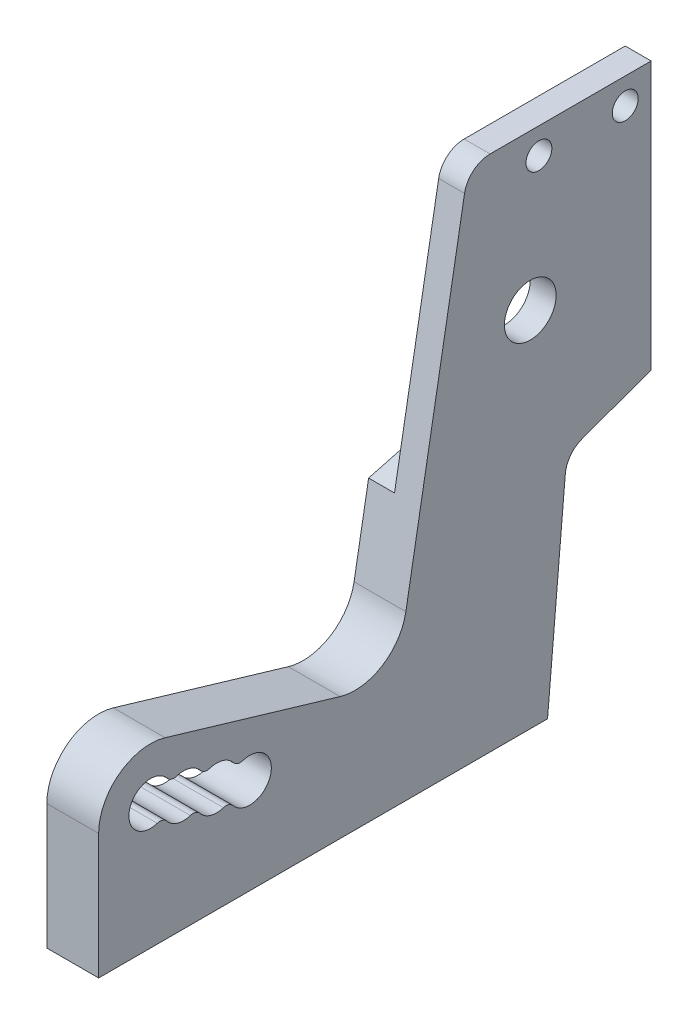
SolidWorks part; units mm, degrees
material "1060 Alloy"
ref_plane "Front Plane" through (0, 0, 0) normal (0, 0, 1) x (1, 0, 0)
ref_plane "Top Plane" through (0, 0, 0) normal (0, 1, 0) x (1, 0, 0)
ref_plane "Right Plane" through (0, 0, 0) normal (1, 0, 0) x (0, 0, -1)
sketch "Sketch1" plane through (0, 0, 0) normal (1, 0, 0) x (0, 0, -1)
  line L1 (0, 0) -> (64, 0)
  line L2 (0, 0) -> (0, 60)
  line L3 (0, 60) -> (64, 60)
  line L4 (64, 0) -> (64, 60)
  circle A0 centre (6, 14.5) radius 2.5
  circle A1 centre (50, 42) radius 3
  dimension "D1" = 6
  dimension "D2" = 5
  dimension "D3" = 14.5
  dimension "D4" = 6
  dimension "D5" = 42
  dimension "D6" = 50
  dimension "D7" = 64
  dimension "D8" = 60
extrude "Boss-Extrude1" add sketch "Sketch1" along normal blind 6
sketch "Sketch2" plane through (6, 0, 0) normal (1, 0, 0) x (0, 0, -1)
  line L0 (0, 60) -> (0, 0) construction
  line L1 (0, 0) -> (64, 0) construction
  line L2 (7.7045, 20.2528) -> (27.9735, 14.2472)
  line L4 (0, 14.5) -> (0, 61)
  line L5 (0, 61) -> (43, 61)
  line L6 (43, 61) -> (35.5869, 18.9581)
  line L7 (64, 60) -> (0, 60) construction
  arc A0 (0, 14.5) -> (7.7045, 20.2528) centre (6, 14.5) cw
  circle A1 centre (50, 42) radius 5 construction
  circle A2 centre (6, 14.5) radius 2.5 construction
  arc A4 (27.9735, 14.2472) -> (35.5869, 18.9581) centre (29.678, 20) ccw
  dimension "D2" = 10
  dimension "D4" = 80
  dimension "D1" = 1
  dimension "D3" = 43
  dimension "D5" = 20
extrude "Cut-Extrude1" cut sketch "Sketch2" against normal up to next
sketch "Sketch3" plane through (6, 0, 0) normal (1, 0, 0) x (0, 0, -1)
  line L2 (0, 0) -> (64, 0) construction
  line L57 (64, 0) -> (52, 0)
  line L58 (64, 0) -> (64, 29)
  line L59 (64, 29) -> (54.2259, 25.4425)
  line L60 (52, 0) -> (54.2259, 25.4425)
  dimension "D1" = 52
  dimension "D2" = 29
  dimension "D3" = 70
  dimension "D4" = 85
extrude "Cut-Extrude2" cut sketch "Sketch3" against normal up to next
fillet "Fillet1" radius 3 1 edges at (3, 60, -42.8237)
fillet "Fillet2" radius 3 1 edges at (3, 25.4425, -54.2259)
hole_wizard "Tap Drill for M3 Tap1" positions "Sketch5" profile "Sketch4" hole size "M3" standard "ISO"
sketch "Sketch5" plane through (0, 0, 0) normal (0, -1, 0) x (-1, 0, 0)
  line L1 (-6, 0) -> (0, 0) construction
  line L2 (-6, 0) -> (-6, 52) construction
  point P0 (-3, 46)
  point P2 (-3, 10)
  dimension "D1" = 3
  dimension "D2" = 10
  dimension "D3" = 36
sketch "Sketch4" plane through (3, 0, -46) normal (1, 0, 0) x (0, 0, -1)
  line L0 (0, 0) -> (0, 9.7511)
  line L1 (0, 9.7511) -> (1.25, 9)
  line L2 (1.25, 9) -> (1.25, 0)
  line L5 (1.25, 0) -> (0, 0)
  line L10 (0, 9.7511) -> (-1.25, 9) construction
  line L11 (0, -6.35) -> (0, 107.95) construction
  dimension "Hole Dia." = 2.5
  dimension "Hole Depth" = 9
  dimension "Drill Angle" = 118
sketch "Sketch9" plane through (0, 0, 0) normal (-1, 0, 0) x (0, 0, 1)
  line L0 (-64, 60) -> (-64, 33)
  line L1 (-64, 60) -> (-45.341, 60) construction
  line L3 (-64, 29) -> (-64, 60) construction
  line L4 (-64, 60) -> (-42.8237, 60)
  line L5 (-42.8237, 60) -> (-37.2725, 28.5179)
  line L6 (-54, 33) -> (-64, 33)
  line L11 (-35.5869, 18.9581) -> (-42.3865, 57.5209) construction
  line L12 (-37.2725, 28.5179) -> (-54, 33)
  dimension "D1" = 10
  dimension "D2" = 27
  dimension "D5" = 65
extrude "Cut-Extrude3" cut sketch "Sketch9" against normal blind 3
sketch "Sketch10" plane through (3, 0, 0) normal (-1, 0, 0) x (0, 0, 1)
  line L0 (-45.341, 60) -> (-64, 60) construction
  line L1 (-64, 60) -> (-64, 33) construction
  circle A0 centre (-61, 57) radius 1.5
  circle A1 centre (-51, 57) radius 1.5
  dimension "D1" = 3
  dimension "D2" = 3
  dimension "D3" = 3
  dimension "D4" = 10
extrude "Cut-Extrude4" cut sketch "Sketch10" against normal up to next
sketch "Sketch11" plane through (0, 0, 0) normal (-1, 0, 0) x (0, 0, 1)
  line L0 (-6, 14.5) -> (-26.269, 8.4944) construction
  line L1 (-7.7045, 20.2528) -> (-27.9735, 14.2472) construction
  circle A0 centre (-9.8352, 13.3637) radius 2.5
  circle A1 centre (-6, 14.5) radius 2.5 construction
  dimension "D1" = 4
extrude "Cut-Extrude5" cut sketch "Sketch11" against normal up to next
pattern_linear "LPattern1" count 3 spacing 4 along (0, -0.2841, -0.9588) of "Cut-Extrude5"
fillet "Fillet3" radius 1 6 edges at (3, 12.4936, -7.4915) (3, 11.3573, -11.3267) (3, 10.2209, -15.1619) (3, 15.37, -8.3437) (3, 14.2337, -12.1789) (3, 13.0973, -16.0141)
